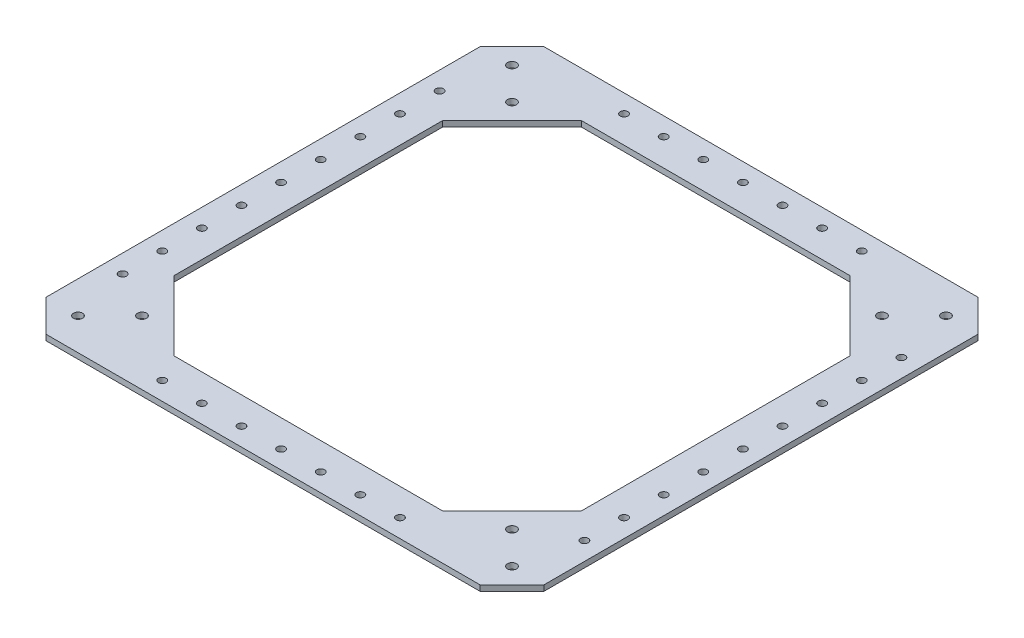
SolidWorks part; units mm, degrees
ref_plane "Front Plane" through (0, 0, 0) normal (0, 0, 1) x (1, 0, 0)
ref_plane "Top Plane" through (0, 0, 0) normal (0, 1, 0) x (1, 0, 0)
ref_plane "Right Plane" through (0, 0, 0) normal (1, 0, 0) x (0, 0, -1)
sketch "Sketch1" plane through (0, 0, 0) normal (0, 1, 0) x (1, 0, 0)
  line L0 (-139.7, 73.5201) -> (-121.7395, 91.4807)
  line L1 (-121.7395, 91.4807) -> (121.7395, 91.4807)
  line L2 (-139.7, 73.5201) -> (-139.7, -169.9588)
  line L3 (139.7, 73.5201) -> (139.7, -169.9588)
  line L4 (139.7, 73.5201) -> (121.7395, 91.4807)
  line L5 (0, 91.4807) -> (0, -187.9193) construction
  line L6 (-139.7, -48.2193) -> (139.7, -48.2193) construction
  line L7 (139.7, -169.9588) -> (121.7395, -187.9193)
  line L8 (-121.7395, -187.9193) -> (121.7395, -187.9193)
  line L9 (-139.7, -169.9588) -> (-121.7395, -187.9193)
  line L10 (-247.4631, 199.2437) -> (247.4631, 199.2437) construction
  line L11 (247.4631, 199.2437) -> (247.4631, -295.6824) construction
  line L12 (247.4631, -295.6824) -> (-247.4631, -295.6824) construction
  line L13 (-247.4631, -295.6824) -> (-247.4631, 199.2437) construction
  line L14 (-247.4631, 199.2437) -> (247.4631, -295.6824) construction
  line L15 (-247.4631, -295.6824) -> (247.4631, 199.2437) construction
  line L16 (-247.4631, 199.2437) -> (-130.7197, 82.5004) construction
  point P11 (0, -48.2193)
  point P20 (0, -48.2193)
  point P21 (-130.7197, 82.5004)
  dimension "D1" = 279.4
  dimension "D2" = 279.4
  dimension "D3" = 25.4
  dimension "D4" = 165.1
extrude "Boss-Extrude1" add sketch "Sketch1" along normal blind 3.175
sketch "Sketch2" plane through (0, 3.175, 0) normal (0, 1, 0) x (1, 0, 0)
  line L0 (-139.7, -48.2193) -> (139.7, -48.2193) construction
  line L1 (-139.7, 73.5201) -> (-139.7, -169.9588) construction
  line L2 (-103.779, 37.5991) -> (-114.3, 27.0781)
  line L3 (0, 91.4807) -> (0, -187.9193) construction
  line L4 (-85.8185, 55.5596) -> (-75.2974, 66.0807)
  line L5 (-130.7197, 82.5004) -> (-94.7987, 46.5794) construction
  line L6 (121.7395, 91.4807) -> (-121.7395, 91.4807) construction
  line L7 (-121.7395, -187.9193) -> (121.7395, -187.9193) construction
  line L8 (139.7, -169.9588) -> (139.7, 73.5201) construction
  line L9 (-114.3, 27.0781) -> (-114.3, -123.5168)
  line L10 (-121.7395, 91.4807) -> (-139.7, 73.5201) construction
  line L11 (-75.2974, 66.0807) -> (75.2974, 66.0807)
  line L12 (114.3, 27.0781) -> (114.3, -123.5168)
  line L13 (85.8185, 55.5596) -> (103.779, 37.5991)
  line L14 (85.8185, 55.5596) -> (75.2974, 66.0807)
  line L15 (103.779, 37.5991) -> (114.3, 27.0781)
  line L16 (-85.8185, -151.9983) -> (-103.779, -134.0378)
  line L17 (103.779, -134.0378) -> (114.3, -123.5168)
  line L18 (85.8185, -151.9983) -> (75.2974, -162.5193)
  line L19 (85.8185, -151.9983) -> (103.779, -134.0378)
  line L20 (-75.2974, -162.5193) -> (75.2974, -162.5193)
  line L21 (-85.8185, -151.9983) -> (-75.2974, -162.5193)
  line L22 (-103.779, -134.0378) -> (-114.3, -123.5168)
  line L23 (-85.8185, 55.5596) -> (-103.779, 37.5991)
  point P9 (-114.3, -48.2193)
  point P22 (114.3, -48.2193)
  point P26 (-114.3, -48.2193)
  dimension "D3" = 25.4
  dimension "D4" = 25.4
  dimension "D1" = 50.8
  dimension "D2" = 25.4
extrude "Cut-Extrude4" cut sketch "Sketch2" against normal through all
sketch "Sketch5" plane through (0, 3.175, 0) normal (0, 1, 0) x (1, 0, 0)
  line L0 (0, 91.4807) -> (0, -187.9193) construction
  line L1 (121.7395, 91.4807) -> (-121.7395, 91.4807) construction
  line L2 (139.7, -48.2193) -> (-139.7, -48.2193) construction
  line L3 (139.7, -169.9588) -> (139.7, 73.5201) construction
  line L4 (-121.7395, -187.9193) -> (121.7395, -187.9193) construction
  line L5 (-139.7, 73.5201) -> (-139.7, -169.9588) construction
  line L6 (-247.4631, 199.2437) -> (247.4631, 199.2437) construction
  line L7 (247.4631, 199.2437) -> (247.4631, -295.6824) construction
  line L8 (247.4631, -295.6824) -> (-247.4631, -295.6824) construction
  line L9 (-247.4631, -295.6824) -> (-247.4631, 199.2437) construction
  line L10 (139.7, -48.2193) -> (358.8347, -48.2193) construction
  line L11 (0, 91.4807) -> (0, 307.0068) construction
  line L12 (-247.4631, 199.2437) -> (247.4631, -295.6824) construction
  line L13 (247.4631, 199.2437) -> (-247.4631, -295.6824) construction
  line L14 (-121.7395, 91.4807) -> (-139.7, 73.5201) construction
  line L15 (-247.4631, 199.2437) -> (-94.7987, 46.5794) construction
  line L16 (-75.2974, 66.0807) -> (-114.3, 27.0781) construction
  circle A0 centre (-121.7395, 73.5201) radius 2.54
  circle A1 centre (-103.779, 55.5596) radius 2.54
  circle A2 centre (103.779, 55.5596) radius 2.54
  circle A3 centre (121.7395, 73.5201) radius 2.54
  circle A4 centre (121.7395, -169.9588) radius 2.54
  circle A5 centre (103.779, -151.9983) radius 2.54
  circle A6 centre (-103.779, -151.9983) radius 2.54
  circle A7 centre (-121.7395, -169.9588) radius 2.54
  point P9 (247.4631, -48.2193)
  point P19 (0, 199.2437)
  point P39 (0, 0)
  point P40 (0, 0)
  dimension "D2" = 5.08
  dimension "D3" = 5.08
  dimension "D1" = 165.1
  dimension "D4" = 25.4
  dimension "D5" = 12.7
extrude "Cut-Extrude3" cut sketch "Sketch5" against normal through all
sketch "Sketch4" plane through (0, 3.175, 0) normal (0, 1, 0) x (1, 0, 0)
  line L0 (-139.7, -48.2193) -> (171.6111, -48.2193) construction
  line L1 (-139.7, 73.5201) -> (-139.7, -169.9588) construction
  line L2 (121.7395, 91.4807) -> (-121.7395, 91.4807) construction
  line L3 (0, -48.2193) -> (0, -217.7016) construction
  line L4 (139.7, -169.9588) -> (139.7, 73.5201) construction
  line L5 (0, -48.2193) -> (0, 293.0757) construction
  circle A0 centre (0, 81.3207) radius 2.159
  circle A1 centre (-44.45, 81.3207) radius 2.159
  circle A2 centre (44.45, 81.3207) radius 2.159
  circle A3 centre (-22.225, 81.3207) radius 2.159
  circle A4 centre (22.225, 81.3207) radius 2.159
  circle A5 centre (-129.54, -48.2193) radius 2.159
  circle A6 centre (-129.54, -25.9943) radius 2.159
  circle A7 centre (-129.54, -3.7693) radius 2.159
  circle A8 centre (129.54, -48.2193) radius 2.159
  circle A9 centre (129.54, -25.9943) radius 2.159
  circle A10 centre (129.54, -3.7693) radius 2.159
  circle A11 centre (129.54, -92.6693) radius 2.159
  circle A12 centre (129.54, -70.4443) radius 2.159
  circle A13 centre (-129.54, -92.6693) radius 2.159
  circle A14 centre (-129.54, -70.4443) radius 2.159
  circle A15 centre (22.225, -177.7593) radius 2.159
  circle A16 centre (-22.225, -177.7593) radius 2.159
  circle A17 centre (44.45, -177.7593) radius 2.159
  circle A18 centre (-44.45, -177.7593) radius 2.159
  circle A19 centre (0, -177.7593) radius 2.159
  circle A20 centre (-66.675, 81.3207) radius 2.159
  circle A21 centre (66.675, 81.3207) radius 2.159
  circle A22 centre (-129.54, 18.4557) radius 2.159
  circle A23 centre (129.54, 18.4557) radius 2.159
  circle A24 centre (129.54, -114.8943) radius 2.159
  circle A25 centre (66.675, -177.7593) radius 2.159
  circle A26 centre (-66.675, -177.7593) radius 2.159
  circle A27 centre (-129.54, -114.8943) radius 2.159
  circle A28 centre (-129.54, -137.1193) radius 2.159
  circle A29 centre (-129.54, 40.6807) radius 2.159
  circle A30 centre (129.54, 40.6807) radius 2.159
  circle A31 centre (129.54, -137.1193) radius 2.159
  point P48 (0, 91.4807)
  point P77 (0, 0)
  point P78 (0, 0)
  dimension "D1" = 4.318
  dimension "D2" = 4.318
  dimension "D3" = 4.318
  dimension "D4" = 4.318
  dimension "D5" = 4.318
  dimension "D6" = 4.318
  dimension "D7" = 4.318
  dimension "D8" = 4.318
  dimension "D9" = 4.318
  dimension "D10" = 4.318
  dimension "D11" = 4.318
  dimension "D23" = 4.318
  dimension "D24" = 4.318
  dimension "D27" = 4.318
  dimension "D28" = 4.318
  dimension "D31" = 4.318
  dimension "D12" = 22.225
  dimension "D13" = 22.225
  dimension "D14" = 22.225
  dimension "D15" = 22.225
  dimension "D16" = 22.225
  dimension "D17" = 22.225
  dimension "D18" = 22.225
  dimension "D19" = 22.225
  dimension "D20" = 10.16
  dimension "D21" = 10.16
  dimension "D22" = 10.16
  dimension "D25" = 22.225
  dimension "D26" = 22.225
  dimension "D29" = 22.225
  dimension "D30" = 22.225
  dimension "D32" = 22.225
extrude "Cut-Extrude2" cut sketch "Sketch4" against normal through all
